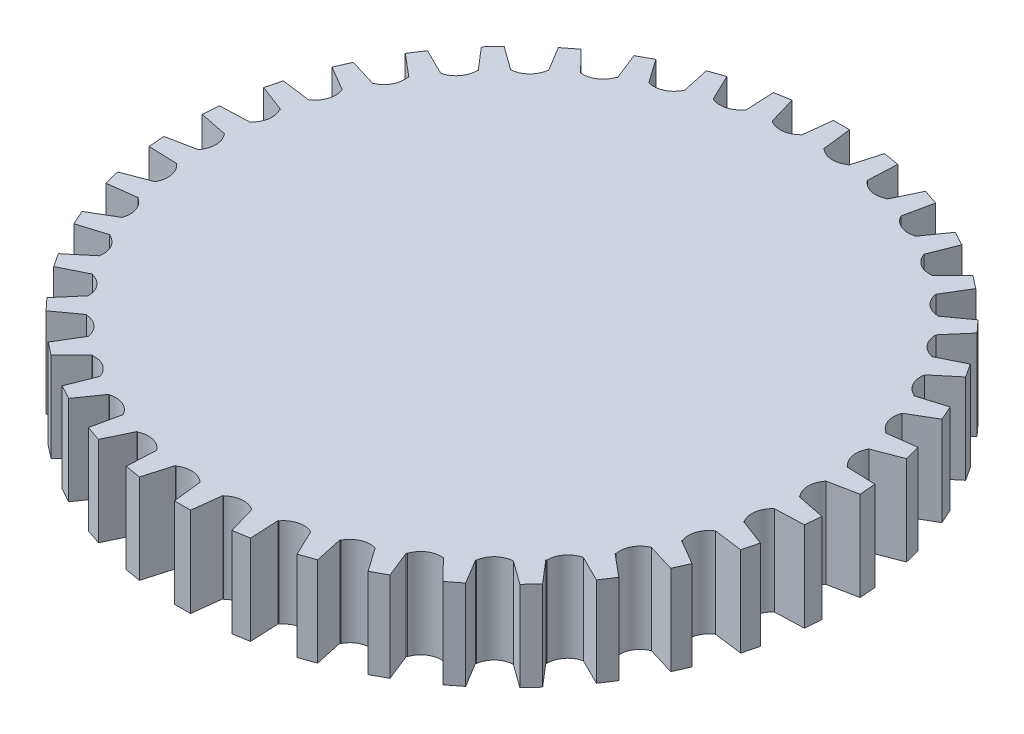
SolidWorks part; units mm, degrees
ref_plane "Front Plane" through (0, 0, 0) normal (0, 0, 1) x (1, 0, 0)
ref_plane "Top Plane" through (0, 0, 0) normal (0, 1, 0) x (1, 0, 0)
ref_plane "Right Plane" through (0, 0, 0) normal (1, 0, 0) x (0, 0, -1)
sketch "Sketch1" plane through (0, 0, 0) normal (0, 1, 0) x (1, 0, 0)
  circle A0 centre (0, 0) radius 21.336
  dimension "D1" = 42.672
extrude "Boss-Extrude1" add sketch "Sketch1" along normal blind 6.35
ref_axis "Axis1" through (0, 6.35, 0) along (0, -1, 0)
sketch "Sketch2" plane through (0, 6.35, 0) normal (0, 1, 0) x (1, 0, 0)
  line L0 (-0.5715, 23.368) -> (0.5715, 23.368)
  line L1 (0.5715, 23.368) -> (0.8129, 21.3205)
  line L2 (-0.5715, 23.368) -> (-0.8129, 21.3205)
  circle A0 centre (0, 0) radius 21.336 construction
  arc A1 (0.8129, 21.3205) -> (2.6544, 21.1702) centre (1.8249, 22.3628) ccw
  arc A4 (0.8129, 21.3205) -> (2.6544, 21.1702) centre (0, 0) cw
  arc A5 (-0.8129, 21.3205) -> (2.6544, 21.1702) centre (0, 0) cw
  point P2 (0, 23.368)
  circle M6 centre (0, 0) radius 21.336
  dimension "D5" = 1.4527
  dimension "D1" = 1.143
  dimension "D2" = 23.368
  dimension "D4" = 1.8415
extrude "Boss-Extrude2" add sketch "Sketch2" against normal up to surface (6.35 mm away) contours L0 L2 L1 M6 region at (0, 6.35, -22.2905) up to face at (0, 0, 21.336)
extrude "Cut-Extrude1" cut sketch "Sketch2<4>" against normal through all contours A4 A1 region at (1.7234, 6.35, -21.1197)
sketch "Sketch2<4>" plane through (0, 6.35, 0) normal (0, 1, 0) x (1, 0, 0) same geometry as "Sketch2"
pattern_circular "CirPattern1" count 38 over 360 about axis through (0, 6.35, 0) along (0, -1, 0) of "Boss-Extrude2", "Cut-Extrude1"
